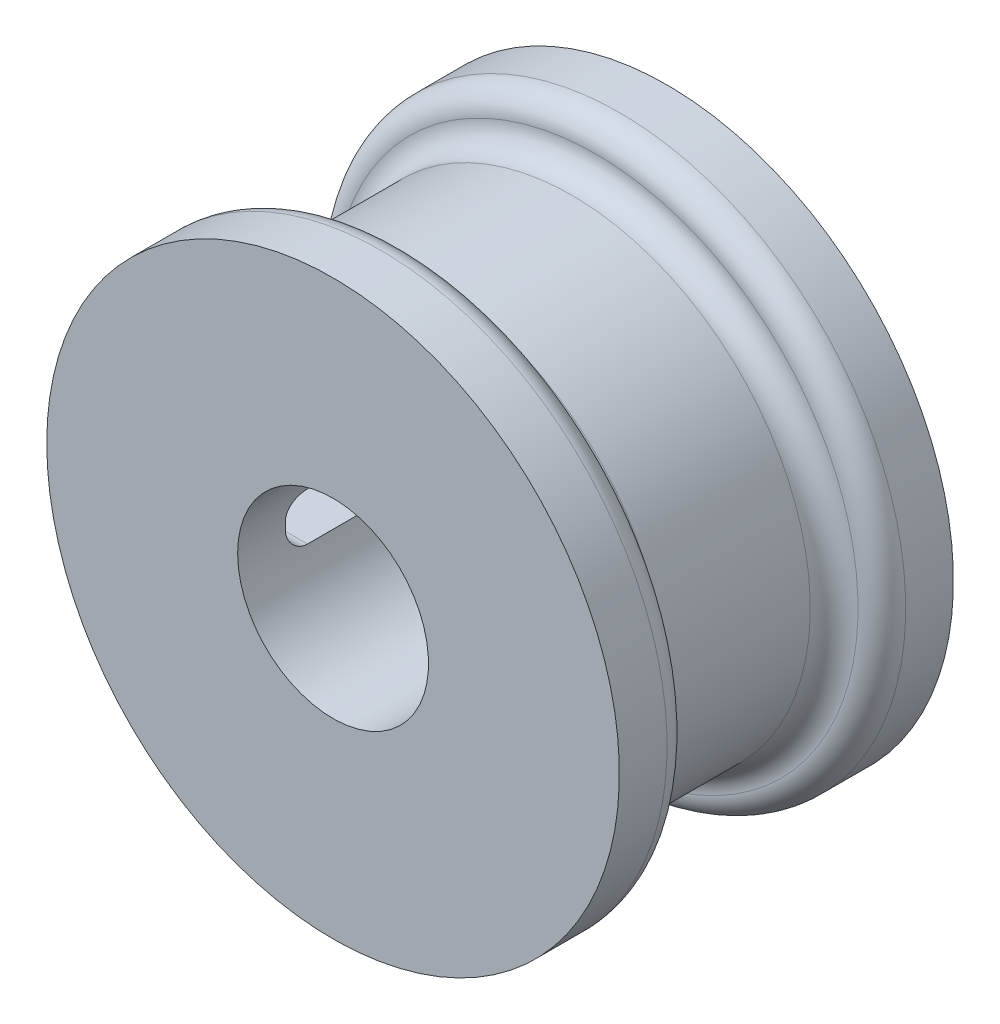
SolidWorks part; units mm, degrees
ref_plane "Front Plane" through (0, 0, 0) normal (0, 0, 1) x (1, 0, 0)
ref_plane "Top Plane" through (0, 0, 0) normal (0, 1, 0) x (1, 0, 0)
ref_plane "Right Plane" through (0, 0, 0) normal (1, 0, 0) x (0, 0, -1)
sketch "Sketch2" plane through (0, 0, 0) normal (0, 1, 0) x (1, 0, 0)
  line L0 (2, 0) -> (6, 0)
  line L1 (-55, 0) -> (55, 0) construction
  line L2 (6, 0) -> (6, 1)
  line L4 (5, 2) -> (5, 5)
  line L6 (6, 6) -> (6, 7)
  line L7 (6, 7) -> (2, 7)
  line L8 (2, 7) -> (2, 0)
  line L9 (0, -55) -> (0, 55) construction
  line L10 (5, 3.5) -> (2, 3.5) construction
  line L11 (2, 7) -> (0, 7) construction
  line L12 (0, 7) -> (0, 0) construction
  line L13 (0, 0) -> (2, 0) construction
  line L14 (5.5, 5.5) -> (2, 5.5) construction
  arc A0 (5.5, 1.5) -> (5, 2) centre (5.5, 2) cw
  arc A1 (5, 5) -> (5.5, 5.5) centre (5.5, 5) cw
  arc A2 (6, 1) -> (5.5, 1.5) centre (5.5, 1) ccw
  arc A3 (6, 6) -> (5.5, 5.5) centre (5.5, 6) cw
  dimension "D5" = 0.5
  dimension "D1" = 5
  dimension "D2" = 3
  dimension "D4" = 7
  dimension "D7" = 3
revolve "Revolve1" add sketch "Sketch2" angle 360 about L12
sketch "Sketch4" plane through (0, 0, 0) normal (1, 0, 0) x (0, 0, -1)
  line L0 (1, 6) -> (1, -6) construction
  line L1 (1.4, -0.5) -> (5.6, -0.5)
  line L2 (1, -0.1) -> (1, 0.1)
  line L3 (1.4, 0.5) -> (5.6, 0.5)
  line L4 (6, -0.1) -> (6, 0.1)
  line L5 (6, 6) -> (6, -6) construction
  line L6 (1, 0) -> (6, 0) construction
  line L7 (3.85, 0) -> (-3.85, 0) construction
  arc A0 (6, 0.1) -> (5.6, 0.5) centre (5.6, 0.1) ccw
  arc A1 (6, -0.1) -> (5.6, -0.5) centre (5.6, -0.1) cw
  arc A2 (1.4, -0.5) -> (1, -0.1) centre (1.4, -0.1) cw
  arc A3 (1, 0.1) -> (1.4, 0.5) centre (1.4, 0.1) cw
  point P14 (6, 0.5)
  point P19 (1, -0.5)
  point P22 (1, 0.5)
  dimension "D2" = 0.4
  dimension "D1" = 1
extrude "Cut-Extrude1" cut sketch "Sketch4" against normal through all
